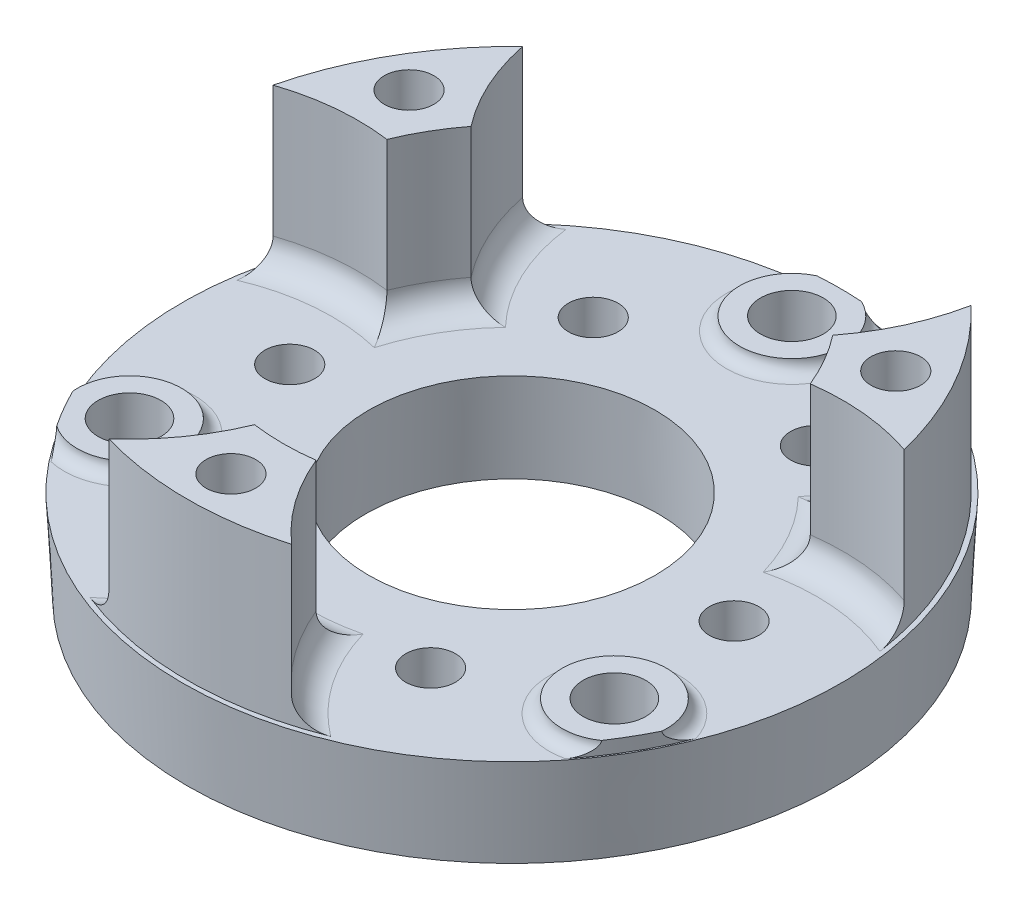
SolidWorks part; units mm, degrees
ref_plane "Alzado" through (0, 0, 0) normal (0, 0, 1) x (1, 0, 0)
ref_plane "Planta" through (0, 0, 0) normal (0, 1, 0) x (1, 0, 0)
ref_plane "Vista lateral" through (0, 0, 0) normal (1, 0, 0) x (0, 0, -1)
sketch "Croquis1" plane through (0, 0, 0) normal (0, 1, 0) x (1, 0, 0)
  circle A0 centre (0, 0) radius 34.7565 construction
  circle A1 centre (0, 0) radius 7.6787 construction
  circle A2 centre (0, 21.4197) radius 13.3367 construction
  circle A3 centre (18.55, -10.7098) radius 13.3368 construction
  circle A4 centre (-18.55, -10.7099) radius 13.3368 construction
  circle A5 centre (0, 0) radius 24.85
  dimension "D1" = 69.5129
  dimension "D2" = 15.3575
  dimension "D3" = 26.6735
  dimension "D5" = 49.7
  dimension "D4" = 3
extrude "Saliente-Extruir1" add sketch "Croquis1" along normal blind 7 draft 3 draft outward yes
sketch "Croquis3" plane through (0, 7, 0) normal (0, 1, 0) x (1, 0, 0)
  circle A0 centre (0, 21.4201) radius 15 construction
  circle A1 centre (18.5503, -10.71) radius 15 construction
  circle A2 centre (-18.5503, -10.71) radius 15 construction
  arc A3 (-2.3552, -17.3408) -> (2.3552, -17.3408) centre (0, 0) ccw
  arc A4 (-6.9887, -23.847) -> (6.9887, -23.847) centre (0, 0) ccw
  arc A5 (-17.1577, 17.9759) -> (-13.84, 10.71) centre (0, 21.4201) ccw
  arc A6 (24.1465, 5.8711) -> (16.1952, 6.6308) centre (18.5503, -10.71) ccw
  arc A7 (-6.9887, -23.847) -> (-2.3552, -17.3408) centre (-18.5503, -10.71) ccw
  arc A8 (-17.1577, 17.9759) -> (-24.1465, 5.8711) centre (0, 0) ccw
  arc A9 (-13.84, 10.71) -> (-16.1952, 6.6308) centre (0, 0) ccw
  arc A10 (24.1465, 5.8711) -> (17.1577, 17.9759) centre (0, 0) ccw
  arc A11 (16.1952, 6.6308) -> (13.84, 10.71) centre (0, 0) ccw
  arc A12 (2.3552, -17.3408) -> (6.9887, -23.847) centre (18.5503, -10.71) ccw
  arc A13 (-16.1952, 6.6308) -> (-24.1465, 5.8711) centre (-18.5503, -10.71) ccw
  arc A14 (13.84, 10.71) -> (17.1577, 17.9759) centre (0, 21.4201) ccw
  dimension "D1" = 30
  dimension "D3" = 35
  dimension "D5" = 17.5
  dimension "D6" = 21.4201
  dimension "D2" = 3
  dimension "D4" = 3
extrude "Saliente-Extruir3" add sketch "Croquis3" along normal blind 12
sketch "Croquis5" plane through (0, 7, 0) normal (0, 1, 0) x (1, 0, 0)
  circle A0 centre (0, 21.4201) radius 2.4
  circle A1 centre (18.5503, -10.71) radius 2.4
  circle A2 centre (-18.5503, -10.71) radius 2.4
  dimension "D2" = 4.8
  dimension "D3" = 21.4201
  dimension "D1" = 3
extrude "Cortar-Extruir2" cut sketch "Croquis5" against normal blind 24
sketch "Croquis20" plane through (0, 19, 0) normal (0, 1, 0) x (1, 0, 0)
  circle A0 centre (-18.6195, 10.75) radius 1.9
  circle A1 centre (0, -21.5) radius 1.9
  circle A2 centre (18.6195, 10.75) radius 1.9
  dimension "D1" = 3.8
  dimension "D2" = 3.8
  dimension "D3" = 3.8
  dimension "D4" = 21.5
extrude "Cortar-Extruir11" cut sketch "Croquis20" against normal blind 6
fillet "Redondeo1" radius 2 3 edges at (4.2958, 7, 20.8618) (15.919, 7, -14.1512) (-4.2958, 7, 20.8618)
fillet "Redondeo2" radius 2 3 edges at (-15.1554, 7, -8.75) (-15.919, 7, -14.1512) (0, 7, 17.5)
fillet "Redondeo3" radius 2 3 edges at (20.2147, 7, -6.7106) (14.6186, 7, -9.6201) (-19.1946, 7, -6.7781)
sketch "Croquis23" plane through (0, 0, 0) normal (0, -1, 0) x (-1, 0, 0)
  circle A0 centre (0, 0) radius 11.2
  dimension "D1" = 22.4
extrude "Cortar-Extruir15" cut sketch "Croquis23" against normal blind 7 draft 2
sketch "Croquis24" plane through (0, 0, 0) normal (0, -1, 0) x (-1, 0, 0)
  line L0 (0, 0) -> (0, -28.3207) construction
  line L1 (0, 0) -> (18.5503, -10.71) construction
  circle A0 centre (18.5503, -10.71) radius 3.25
  circle A1 centre (-18.5503, -10.71) radius 3.25
  circle A2 centre (0, 21.42) radius 3.25
  dimension "D1" = 6.5
  dimension "D3" = 60
  dimension "D4" = 21.42
  dimension "D2" = 3
extrude "Cortar-Extruir16" cut sketch "Croquis24" against normal blind 1
sketch "Croquis25" plane through (0, 7, 0) normal (0, 1, 0) x (1, 0, 0)
  arc A0 (-1.6962, 25.0426) -> (1.6962, 25.0426) centre (0, 21.4201) ccw
  arc A1 (-20.8395, -13.9902) -> (-22.5356, -11.0524) centre (-18.5503, -10.71) ccw
  arc A2 (22.5356, -11.0524) -> (20.8395, -13.9902) centre (18.5503, -10.71) ccw
  arc A3 (1.6962, 25.0426) -> (-1.6962, 25.0426) centre (0, 0) ccw
  arc A4 (20.8395, -13.9902) -> (22.5356, -11.0524) centre (0, 0) ccw
  arc A5 (-22.5356, -11.0524) -> (-20.8395, -13.9902) centre (0, 0) ccw
  circle A6 centre (0, 21.4201) radius 2.4
  circle A7 centre (18.5503, -10.71) radius 2.4
  circle A8 centre (-18.5503, -10.71) radius 2.4
  dimension "D1" = 8
extrude "Saliente-Extruir4" add sketch "Croquis25" along normal blind 1
fillet "Redondeo6" radius 1 3 edges at (15.0862, 7, 8.71) (0, 7, -17.4201) (-15.0862, 7, 8.71)
sketch "Croquis26" plane through (0, 7, 0) normal (0, 1, 0) x (1, 0, 0)
  line L0 (0, 0) -> (0, 45.2223) construction
  line L1 (0, 0) -> (-20.6612, 35.7863) construction
  circle A0 centre (-8.5, 14.7224) radius 1.9
  circle A1 centre (8.5, 14.7224) radius 1.9
  circle A2 centre (17, 0) radius 1.9
  circle A3 centre (8.5, -14.7224) radius 1.9
  circle A4 centre (-8.5, -14.7224) radius 1.9
  circle A5 centre (-17, 0) radius 1.9
  dimension "D1" = 3.8
  dimension "D2" = 30
  dimension "D3" = 17
  dimension "D4" = 6
extrude "Cortar-Extruir17" cut sketch "Croquis26" against normal blind 10
